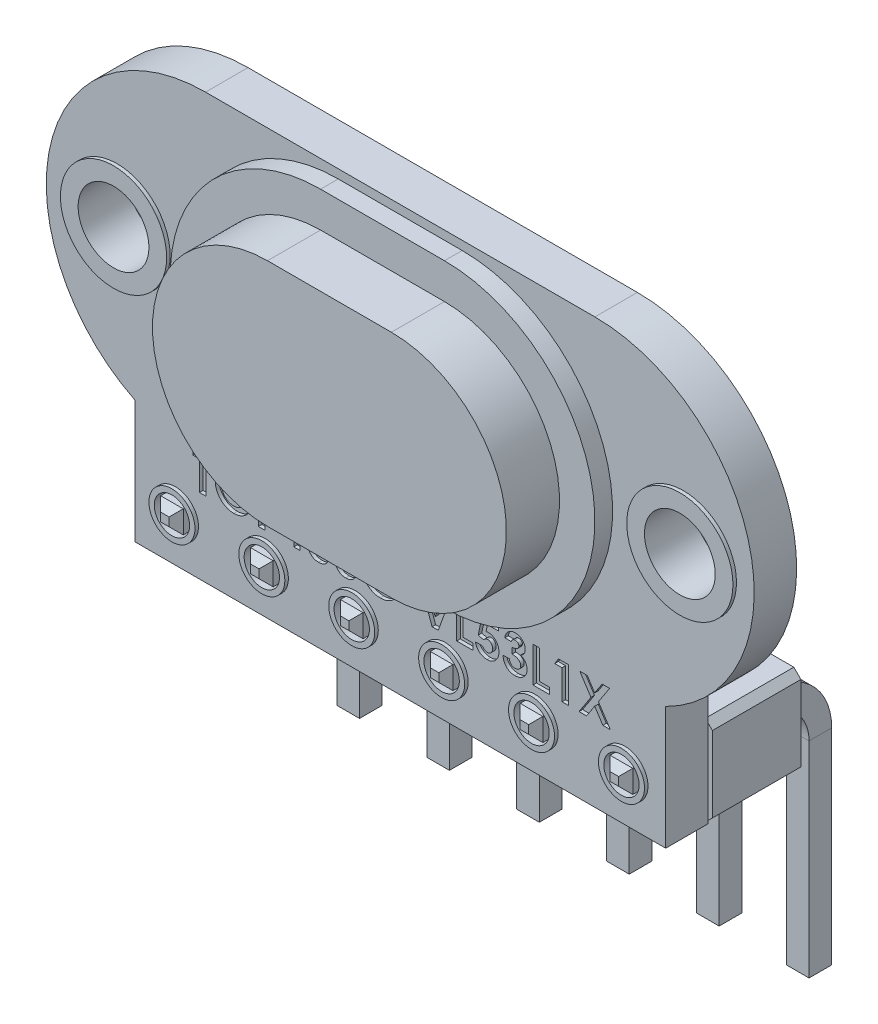
SolidWorks part; units mm, degrees
ref_plane "Plan de face" through (0, 0, 0) normal (0, 0, 1) x (1, 0, 0)
ref_plane "Plan de dessus" through (0, 0, 0) normal (0, 1, 0) x (1, 0, 0)
ref_plane "Plan de droite" through (0, 0, 0) normal (1, 0, 0) x (0, 0, -1)
sketch "Esquisse1" plane through (0, 0, 0) normal (0, 0, 1) x (1, 0, 0)
  line L0 (-7.5, -4.0311) -> (-7.5, -7.5)
  line L1 (0, 19.431) -> (0, -15.0057) construction
  line L2 (-5.5, 0) -> (5.5, 0) construction
  line L5 (-7.5, -7.5) -> (7.5, -7.5)
  line L6 (7.5, -4.0311) -> (7.5, -7.5)
  line L7 (-6.35, -6.23) -> (-3.81, -6.23) construction
  line L8 (-5.5, 4.5) -> (5.5, 4.5)
  circle A2 centre (-8, 0) radius 1
  circle A3 centre (8, 0) radius 1
  circle A4 centre (-6.35, -6.23) radius 0.5
  circle A5 centre (-3.81, -6.23) radius 0.5
  circle A6 centre (-1.27, -6.23) radius 0.5
  circle A7 centre (1.27, -6.23) radius 0.5
  circle A8 centre (3.81, -6.23) radius 0.5
  circle A9 centre (6.35, -6.23) radius 0.5
  arc A10 (-5.5, 4.5) -> (-7.5, -4.0311) centre (-5.5, 0) ccw
  arc A11 (7.5, -4.0311) -> (5.5, 4.5) centre (5.5, 0) ccw
  point P7 (0, 0)
  point P8 (0, 0)
  dimension "D1" = 20
  dimension "D3" = 2
  dimension "D6" = 1
  dimension "D2" = 16
  dimension "D5" = 4.5
  dimension "D4" = 15
  dimension "D8" = 2.54
  dimension "D9" = 1.27
  dimension "D10" = 12
  dimension "D11" = 8.5311
  dimension "D7" = 6
extrude "Boss.-Extru.1" add sketch "Esquisse1" along normal mid plane 1.2
sketch "Esquisse2" plane through (0, 0, 0.6) normal (0, 0, 1) x (1, 0, 0)
  line L0 (-1.75, 0) -> (1.75, 0) construction
  line L1 (-1.75, 4.25) -> (1.75, 4.25)
  line L2 (-1.75, -4.25) -> (1.75, -4.25)
  arc A0 (-1.75, 4.25) -> (-1.75, -4.25) centre (-1.75, 0) ccw
  arc A1 (1.75, -4.25) -> (1.75, 4.25) centre (1.75, 0) ccw
  point P3 (0, 0)
  dimension "D2" = 12
  dimension "D1" = 8.5
extrude "Boss.-Extru.2" add sketch "Esquisse2" along normal blind 0.5
sketch "Esquisse4" plane through (0, 0, 1.1) normal (0, 0, 1) x (1, 0, 0)
  line L4 (-1.75, -3.25) -> (1.75, -3.25)
  line L5 (1.75, 3.25) -> (-1.75, 3.25)
  line L6 (-1.75, -3.25) -> (1.75, -3.25)
  line L7 (1.75, 3.25) -> (-1.75, 3.25)
  arc A4 (-1.75, 3.25) -> (-1.75, -3.25) centre (-1.75, 0) ccw
  arc A5 (1.75, -3.25) -> (1.75, 3.25) centre (1.75, 0) ccw
  arc A6 (-1.75, 3.25) -> (-1.75, -3.25) centre (-1.75, 0) ccw
  arc A7 (1.75, -3.25) -> (1.75, 3.25) centre (1.75, 0) ccw
  dimension "D1" = 1
extrude "Boss.-Extru.4" add sketch "Esquisse4" along normal blind 1.5
sketch "Esquisse3" plane through (0, 0, 0.6) normal (0, 0, 1) x (1, 0, 0)
  line L0 (-6.35, -6.23) -> (-3.81, -6.23) construction
  circle A0 centre (-8, 0) radius 1.5
  circle A1 centre (8, 0) radius 1.5
  circle A2 centre (8, 0) radius 1 construction
  circle A3 centre (-8, 0) radius 1 construction
  circle A4 centre (8, 0) radius 1
  circle A5 centre (-8, 0) radius 1
  circle A6 centre (-6.35, -6.23) radius 0.65
  circle A7 centre (-6.35, -6.23) radius 0.5 construction
  circle A8 centre (-3.81, -6.23) radius 0.65
  circle A9 centre (-1.27, -6.23) radius 0.65
  circle A10 centre (1.27, -6.23) radius 0.65
  circle A11 centre (3.81, -6.23) radius 0.65
  circle A12 centre (6.35, -6.23) radius 0.65
  circle A13 centre (6.35, -6.23) radius 0.5 construction
  circle A14 centre (3.81, -6.23) radius 0.5 construction
  circle A15 centre (1.27, -6.23) radius 0.5 construction
  circle A16 centre (-1.27, -6.23) radius 0.5 construction
  circle A17 centre (-3.81, -6.23) radius 0.5 construction
  circle A18 centre (6.35, -6.23) radius 0.5
  circle A19 centre (3.81, -6.23) radius 0.5
  circle A20 centre (1.27, -6.23) radius 0.5
  circle A21 centre (-1.27, -6.23) radius 0.5
  circle A22 centre (-3.81, -6.23) radius 0.5
  circle A23 centre (-6.35, -6.23) radius 0.5
  dimension "D1" = 3
  dimension "D2" = 1.3
  dimension "D4" = 2.54
  dimension "D3" = 6
extrude "Boss.-Extru.3" add sketch "Esquisse3" along normal blind 0.1
sketch "Esquisse5" plane through (0, 0, 0.6) normal (0, 0, 1) x (1, 0, 0)
  line L0 (-7.5, -5.3812) -> (7.5, -5.3812) construction
  line L1 (-7.5, -4.0311) -> (-7.5, -7.5) construction
  line L2 (7.5, -7.5) -> (7.5, -4.0311) construction
  text T0 "<b>TOF400C-VL53L1X</b>" font "Century Gothic" height 1
extrude "Enlèv. mat.-Extru.1" cut sketch "Esquisse5" against normal blind 0.1
mirror "Symétrie1" about plane through (0, 0, 0) normal (0, 0, 1) of "Boss.-Extru.3"
sketch "Esquisse6" plane through (0, 0, -0.6) normal (0, 0, -1) x (-1, 0, 0)
  line L0 (-5.5521, -5.2944) -> (-5.5521, 1.9609) construction
  text T0 "<b>VIN</b>\r\n<b>GND</b>\r\n<b>SDA</b>\r\n<b>SCL</b>\r\n<b>INT</b>\r\n<b>SHUT</b>" font "Century Gothic" height 1.46
extrude "Enlèv. mat.-Extru.2" cut sketch "Esquisse6" against normal blind 0.1
sketch "Esquisse7" plane through (0, 0, -0.6) normal (0, 0, -1) x (-1, 0, 0)
  line L0 (-7.62, -5.16) -> (-7.42, -4.96)
  line L1 (-7.42, -7.5) -> (-5.28, -7.5)
  line L2 (-7.62, -7.3) -> (-7.62, -5.16)
  line L3 (-7.42, -4.96) -> (-5.28, -4.96)
  line L4 (-5.08, -7.3) -> (-5.08, -5.16)
  line L5 (-7.62, -7.5) -> (-5.08, -4.96) construction
  line L6 (-7.62, -4.96) -> (-5.08, -7.5) construction
  line L7 (-5.28, -4.96) -> (-5.08, -5.16)
  line L8 (-5.28, -7.5) -> (-5.08, -7.3)
  line L9 (-7.62, -7.3) -> (-7.42, -7.5)
  point P0 (-6.35, -6.23)
  dimension "D1" = 2.54
extrude "Boss.-Extru.5" add sketch "Esquisse7" along normal blind 2.5
ref_plane "Plan1" through (6.35, 0, 0) normal (1, 0, 0) x (0, 0, -1)
sketch "Esquisse8" plane through (6.35, 0, 0) normal (1, 0, 0) x (0, 0, -1)
  line L0 (-0.9, -6.23) -> (3.1, -6.23)
  line L1 (4.6, -7.73) -> (4.6, -13.73)
  line L2 (3.1, -4.96) -> (0.6, -4.96) construction
  line L3 (3.1, -7.5) -> (0.6, -7.5) construction
  line L4 (3.1, -5.16) -> (3.1, -7.3) construction
  arc A0 (3.1, -6.23) -> (4.6, -7.73) centre (3.1, -7.73) cw
  dimension "D3" = 4
  dimension "D1" = 7.5
  dimension "D2" = 6
ref_plane "Plan2" through (6.35, -13.73, -4.6) normal (0, -1, 0) x (-1, 0, 0)
sketch "Esquisse9" plane through (6.35, -13.73, -4.6) normal (0, -1, 0) x (-1, 0, 0)
  line L1 (0.32, -0.32) -> (-0.32, -0.32)
  line L2 (0.32, -0.32) -> (0.32, 0.32)
  line L3 (0.32, 0.32) -> (-0.32, 0.32)
  line L4 (-0.32, -0.32) -> (-0.32, 0.32)
  line L5 (0.32, -0.32) -> (-0.32, 0.32) construction
  line L6 (0.32, 0.32) -> (-0.32, -0.32) construction
  point P0 (0, 0)
  dimension "D1" = 0.64
sweep "Balayage1" add profiles "Esquisse9" path "Esquisse8"
chamfer "Chanfrein1" distance 0.2 angle 45 8 edges at (6.35, -6.55, 0.9) (6.03, -6.23, 0.9) (6.35, -5.91, 0.9) (6.67, -6.23, 0.9) (6.35, -13.73, -4.92) (6.03, -13.73, -4.6) (6.35, -13.73, -4.28) (6.67, -13.73, -4.6)
pattern_linear "Répétition linéaire2" count 6 spacing 2.54 along (-1, 0, 0) of "Boss.-Extru.5", "Balayage1", "Chanfrein1"
